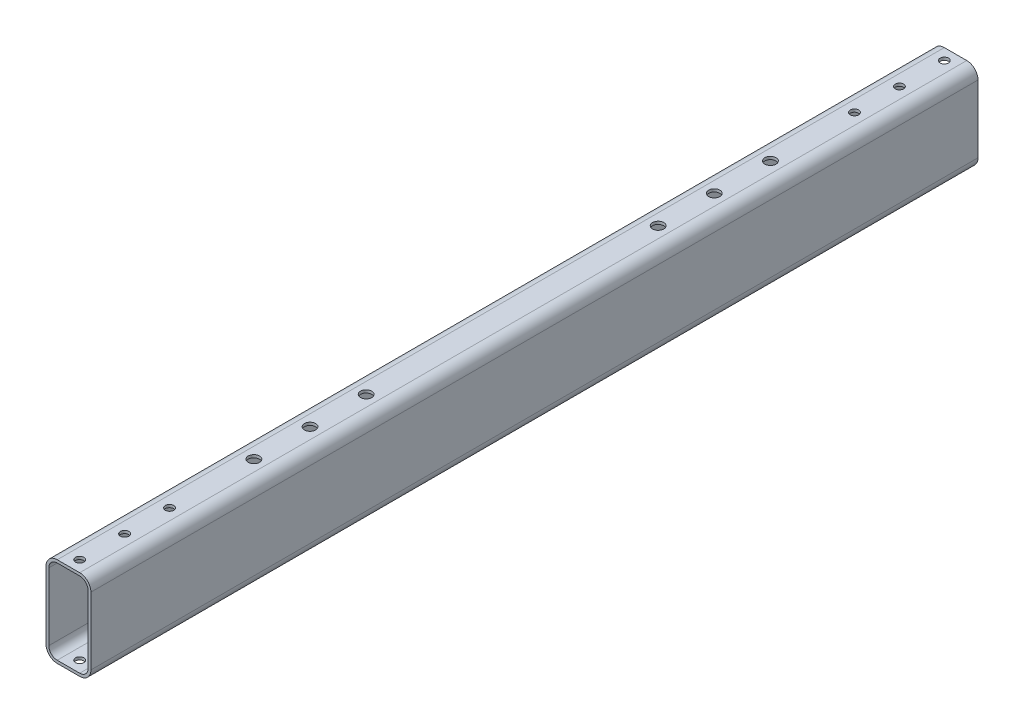
SolidWorks part; units mm, degrees
material "6061-T6 (SS)"
ref_plane "Front Plane" through (0, 0, 0) normal (0, 0, 1) x (1, 0, 0)
ref_plane "Top Plane" through (0, 0, 0) normal (0, 1, 0) x (1, 0, 0)
ref_plane "Right Plane" through (0, 0, 0) normal (1, 0, 0) x (0, 0, -1)
sketch "Sketch1" plane through (0, 0, 0) normal (0, 0, 1) x (1, 0, 0)
  line L1 (-6.35, -25.4) -> (6.35, -25.4)
  line L2 (-12.7, -19.05) -> (-12.7, 19.05)
  line L3 (-6.35, 25.4) -> (6.35, 25.4)
  line L4 (12.7, -19.05) -> (12.7, 19.05)
  line L5 (-12.7, -25.4) -> (12.7, 25.4) construction
  line L6 (-12.7, 25.4) -> (12.7, -25.4) construction
  arc A0 (-12.7, -19.05) -> (-6.35, -25.4) centre (-6.35, -19.05) ccw
  arc A1 (6.35, -25.4) -> (12.7, -19.05) centre (6.35, -19.05) ccw
  arc A2 (6.35, 25.4) -> (12.7, 19.05) centre (6.35, 19.05) cw
  arc A3 (-12.7, 19.05) -> (-6.35, 25.4) centre (-6.35, 19.05) cw
  point P0 (0, 0)
  dimension "D3" = 6.35
  dimension "D1" = 50.8
  dimension "D2" = 25.4
extrude "Extrude-Thin1" add sketch "Sketch1" along normal blind 501.65 thin thin type one direction reverse wall 1.5875
hole_wizard "3/16 (0.1875) Diameter Hole1" positions "3DSketch1" profile "Sketch3" hole size "3/16" standard "ANSI Inch" end condition through all
sketch3d "3DSketch1"
  line L1 (6.35, 25.4, 0) -> (-6.35, 25.4, 0) construction
  line L6 (0, 25.4, 501.65) -> (0, 25.4, 0) construction
  line L7 (6.35, 25.4, 501.65) -> (-6.35, 25.4, 501.65) construction
  point P57 (0, 25.4, 6.35)
  point P59 (0, 25.4, 31.75)
  point P61 (0, 25.4, 57.15)
  point P63 (0, 25.4, 469.9)
  point P65 (0, 25.4, 444.5)
  point P67 (0, 25.4, 495.3)
  dimension "D1" = 25.4
  dimension "D2" = 25.4
  dimension "D3" = 6.35
  dimension "D4" = 25.4
  dimension "D5" = 25.4
  dimension "D6" = 6.35
sketch "Sketch3" plane through (0, 25.4, 495.3) normal (1, 0, 0) x (0, 0, 1)
  line L0 (0, 0) -> (0, 50.8)
  line L1 (0, 50.8) -> (2.3812, 50.8)
  line L2 (2.3812, 50.8) -> (2.3812, 0)
  line L5 (2.3812, 0) -> (0, 0)
  line L11 (0, -6.35) -> (0, 107.95) construction
  dimension "Thru Hole Dia." = 4.7625
  dimension "Thru Hole Depth" = 50.8
hole_wizard "3/16 (0.195) Diameter Hole1" positions "Sketch4" profile "Sketch5" hole size "3/16" standard "ANSI Inch" end condition up to next
sketch "Sketch4" plane through (0, -25.4, 0) normal (0, -1, 0) x (-1, 0, 0)
  point P6 (-3.175, -88.3553)
  point P9 (3.175, -113.7553)
  point P15 (-3.175, -342.3553)
  point P18 (3.175, -316.9553)
  point P29 (-3.175, -139.1553)
  point P34 (3.175, -164.5553)
  point P39 (3.175, -367.7553)
sketch "Sketch5" plane through (3.175, -25.4, 88.3553) normal (1, 0, 0) x (0, 0, -1)
  line L0 (0, 0) -> (0, 1.5875)
  line L1 (0, 1.5875) -> (2.4765, 1.5875)
  line L2 (2.4765, 1.5875) -> (2.4765, 0)
  line L5 (2.4765, 0) -> (0, 0)
  line L11 (0, -6.35) -> (0, 107.95) construction
  dimension "Thru Hole Dia." = 4.953
  dimension "Thru Hole Depth" = 1.5875
hole_wizard "1/4 (0.25) Diameter Hole1" positions "Sketch6" profile "Sketch7" hole size "1/4" standard "ANSI Inch"
sketch "Sketch6" plane through (0, 25.4, 0) normal (0, 1, 0) x (1, 0, 0)
  point P0 (0, -104.6752)
  point P3 (0, -136.4252)
  point P6 (0, -168.1752)
  point P9 (0, -396.8)
  point P12 (0, -365.05)
  point P15 (0, -333.3)
sketch "Sketch7" plane through (0, 25.4, 104.6752) normal (1, 0, 0) x (0, 0, 1)
  line L0 (0, 0) -> (0, 27.3077)
  line L1 (0, 27.3077) -> (3.175, 25.4)
  line L2 (3.175, 25.4) -> (3.175, 0)
  line L5 (3.175, 0) -> (0, 0)
  line L10 (0, 27.3077) -> (-3.175, 25.4) construction
  line L11 (0, -6.35) -> (0, 107.95) construction
  dimension "Hole Dia." = 6.35
  dimension "Hole Depth" = 25.4
  dimension "Drill Angle" = 118
